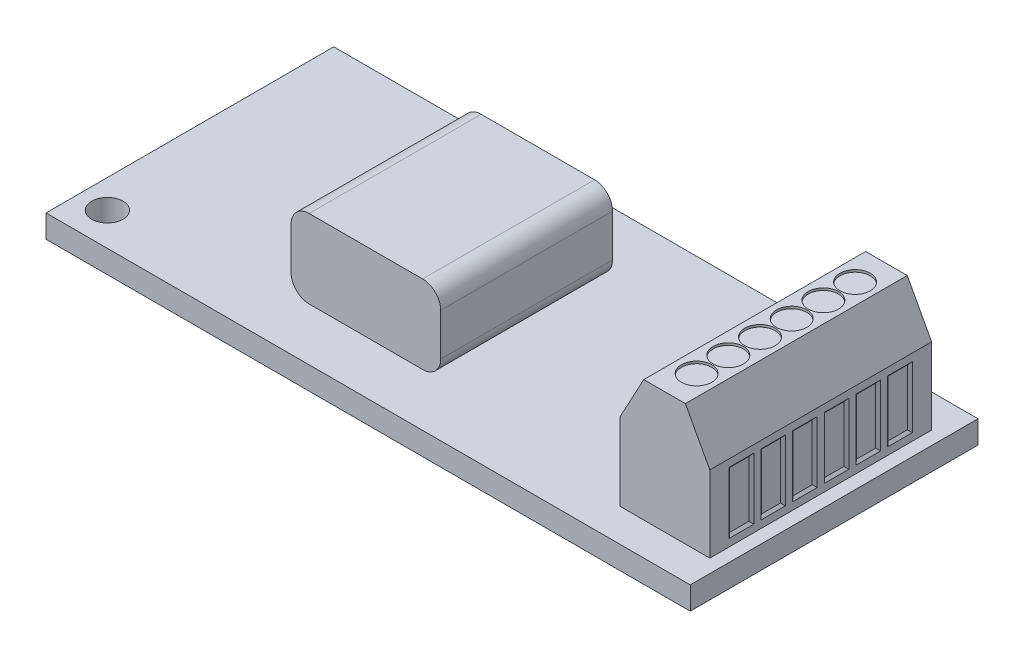
SolidWorks part; units mm, degrees
ref_plane "Front Plane" through (0, 0, 0) normal (0, 0, 1) x (1, 0, 0)
ref_plane "Top Plane" through (0, 0, 0) normal (0, 1, 0) x (1, 0, 0)
ref_plane "Right Plane" through (0, 0, 0) normal (1, 0, 0) x (0, 0, -1)
ref_axis "Axis1" through (-88.99, 0, 0) along (1, 0, 0)
ref_axis "Axis2" through (0, 55, 0) along (0, -1, 0)
ref_axis "Axis3" through (0, 0, 55) along (0, 0, -1)
ref_point "Point1"
sketch "Sketch1" plane through (0, 0, 0) normal (0, 1, 0) x (1, 0, 0)
  line L1 (-22.606, -10.0965) -> (22.606, -10.0965)
  line L2 (-22.606, -10.0965) -> (-22.606, 10.0965)
  line L3 (-22.606, 10.0965) -> (22.606, 10.0965)
  line L4 (22.606, -10.0965) -> (22.606, 10.0965)
  line L5 (-22.606, -10.0965) -> (22.606, 10.0965) construction
  line L6 (-22.606, 10.0965) -> (22.606, -10.0965) construction
  point P0 (0, 0)
  dimension "D1" = 20.193
  dimension "D2" = 45.212
extrude "Boss-Extrude1" add sketch "Sketch1" along normal mid plane 1.6002
sketch "Sketch2" plane through (0, 0.8001, 0) normal (0, 1, 0) x (1, 0, 0)
  line L0 (22.606, -10.0965) -> (22.606, 10.0965) construction
  line L1 (15.367, -7.7851) -> (21.6662, -7.7851)
  line L2 (15.367, -7.7851) -> (15.367, 7.7851)
  line L3 (15.367, 7.7851) -> (21.6662, 7.7851)
  line L4 (21.6662, -7.7851) -> (21.6662, 7.7851)
  line L5 (15.367, -7.7851) -> (21.6662, 7.7851) construction
  line L6 (15.367, 7.7851) -> (21.6662, -7.7851) construction
  line L7 (18.5166, 0) -> (0, 0) construction
  point P0 (18.5166, 0)
  dimension "D1" = 0.9398
  dimension "D2" = 6.2992
  dimension "D3" = 15.5702
extrude "Boss-Extrude2" add sketch "Sketch2" along normal blind 8.5344 separate body
sketch "Sketch3" plane through (0, 0, 7.7851) normal (0, 0, 1) x (1, 0, 0)
  line L0 (17.0319, 9.3345) -> (19.9529, 9.3345)
  line L1 (15.367, 9.3345) -> (21.6662, 9.3345) construction
  line L2 (19.9529, 9.3345) -> (21.6662, 6.1595)
  line L3 (21.6662, 9.3345) -> (21.6662, 0.8001) construction
  line L4 (21.6662, 6.1595) -> (21.6662, 9.3345) construction
  line L5 (18.4924, 9.3345) -> (18.4924, 6.9827) construction
  line L6 (17.0319, 9.3345) -> (15.3187, 6.1595)
  line L7 (15.3187, 6.1595) -> (15.3187, 11.2263)
  line L8 (15.3187, 11.2263) -> (21.6662, 11.2263)
  line L9 (21.6662, 11.2263) -> (21.6662, 6.1595)
  point P5 (18.4924, 9.3345)
  dimension "D1" = 2.921
  dimension "D2" = 3.175
sketch "Sketch4" plane through (0, 9.3345, 0) normal (0, 1, 0) x (1, 0, 0)
  line L0 (18.5166, 7.7851) -> (18.5166, 5.5608) construction
  line L2 (18.5166, 5.5608) -> (18.5166, 3.3365) construction
  line L3 (18.5166, 3.3365) -> (18.5166, 1.1122) construction
  line L4 (18.5166, 1.1122) -> (18.5166, -1.1122) construction
  line L5 (18.5166, -1.1122) -> (18.5166, -3.3365) construction
  line L6 (18.5166, -3.3365) -> (18.5166, -5.5608) construction
  line L7 (18.5166, -5.5608) -> (18.5166, -7.7851) construction
  circle A0 centre (18.5166, -5.5608) radius 1.0668
  circle A1 centre (18.5166, -3.3365) radius 1.0668
  circle A2 centre (18.5166, -1.1122) radius 1.0668
  circle A3 centre (18.5166, 1.1122) radius 1.0668
  circle A4 centre (18.5166, 3.3365) radius 1.0668
  circle A5 centre (18.5166, 5.5608) radius 1.0668
  dimension "D1" = 2.1336
sketch "Sketch6" plane through (0, 0.8001, 0) normal (0, 1, 0) x (1, 0, 0)
  line L0 (-21.717, -7.7773) -> (-22.606, -7.7773) construction
  line L1 (-22.606, 10.0965) -> (-22.606, -10.0965) construction
  line L2 (-20.617, -8.8773) -> (-20.617, -10.0965) construction
  line L3 (-22.606, -10.0965) -> (22.606, -10.0965) construction
  line L4 (12.906, 7.7465) -> (22.606, 7.7465) construction
  line L5 (22.606, -10.0965) -> (22.606, 10.0965) construction
  line L6 (11.806, 8.8465) -> (11.806, 10.0965) construction
  line L7 (22.606, 10.0965) -> (-22.606, 10.0965) construction
  circle A0 centre (-20.617, -7.7773) radius 1.1
  circle A1 centre (11.806, 7.7465) radius 1.1
  dimension "D1" = 0.889
  dimension "D3" = 2.2
  dimension "D4" = 9.7
  dimension "D6" = 2.2
  dimension "D2" = 1.2192
  dimension "D5" = 1.25
extrude "Cut-Extrude4" cut sketch "Sketch6" against normal through all
sketch "Sketch7" plane through (0, 0.8001, 0) normal (0, 1, 0) x (1, 0, 0)
  line L0 (-22.606, -10.0965) -> (22.606, -10.0965) construction
  line L1 (-9.106, -6.3965) -> (1.394, -6.3965)
  line L2 (-9.106, -6.3965) -> (-9.106, 5.6665)
  line L3 (-9.106, 5.6665) -> (1.394, 5.6665)
  line L4 (1.394, -6.3965) -> (1.394, 5.6665)
  line L5 (-9.106, -6.3965) -> (1.394, 5.6665) construction
  line L6 (-9.106, 5.6665) -> (1.394, -6.3965) construction
  line L7 (22.606, 10.0965) -> (-22.606, 10.0965) construction
  line L8 (-22.606, 10.0965) -> (-22.606, -10.0965) construction
  point P0 (-3.856, -0.365)
  dimension "D1" = 3.7
  dimension "D2" = 4.43
  dimension "D3" = 10.5
  dimension "D4" = 13.5
extrude "Boss-Extrude3" add sketch "Sketch7" along normal blind 5.5 separate body
extrude "Cut-Extrude5" cut sketch "Sketch3" against normal through all
extrude "Cut-Extrude6" cut sketch "Sketch4" against normal blind 0.1588
sketch "Sketch5" plane through (21.6662, 0, 0) normal (1, 0, 0) x (0, 0, -1)
  line L0 (-7.7851, 3.4798) -> (-5.5608, 3.4798) construction
  line L1 (-7.7851, 6.1595) -> (-7.7851, 0.8001) construction
  line L2 (-5.5608, 3.4798) -> (-3.3365, 3.4798) construction
  line L3 (-3.3365, 3.4798) -> (-1.1122, 3.4798) construction
  line L4 (-1.1122, 3.4798) -> (1.1122, 3.4798) construction
  line L5 (1.1122, 3.4798) -> (3.3365, 3.4798) construction
  line L6 (3.3365, 3.4798) -> (5.5608, 3.4798) construction
  line L7 (5.5608, 3.4798) -> (7.7851, 3.4798) construction
  line L8 (7.7851, 6.1595) -> (7.7851, 0.8001) construction
  line L10 (-6.4244, 1.3208) -> (-4.6972, 1.3208)
  line L11 (-6.4244, 1.3208) -> (-6.4244, 5.6388)
  line L12 (-6.4244, 5.6388) -> (-4.6972, 5.6388)
  line L13 (-4.6972, 1.3208) -> (-4.6972, 5.6388)
  line L14 (-6.4244, 1.3208) -> (-4.6972, 5.6388) construction
  line L15 (-6.4244, 5.6388) -> (-4.6972, 1.3208) construction
  line L16 (-4.2001, 1.3208) -> (-2.4729, 1.3208)
  line L17 (-4.2001, 1.3208) -> (-4.2001, 5.6388)
  line L18 (-4.2001, 5.6388) -> (-2.4729, 5.6388)
  line L19 (-2.4729, 1.3208) -> (-2.4729, 5.6388)
  line L20 (-4.2001, 1.3208) -> (-2.4729, 5.6388) construction
  line L21 (-4.2001, 5.6388) -> (-2.4729, 1.3208) construction
  line L22 (-1.9758, 1.3208) -> (-0.2486, 1.3208)
  line L23 (-1.9758, 1.3208) -> (-1.9758, 5.6388)
  line L24 (-1.9758, 5.6388) -> (-0.2486, 5.6388)
  line L25 (-0.2486, 1.3208) -> (-0.2486, 5.6388)
  line L26 (-1.9758, 1.3208) -> (-0.2486, 5.6388) construction
  line L27 (-1.9758, 5.6388) -> (-0.2486, 1.3208) construction
  line L28 (0.2486, 1.3208) -> (1.9758, 1.3208)
  line L29 (0.2486, 1.3208) -> (0.2486, 5.6388)
  line L30 (0.2486, 5.6388) -> (1.9758, 5.6388)
  line L31 (1.9758, 1.3208) -> (1.9758, 5.6388)
  line L32 (0.2486, 1.3208) -> (1.9758, 5.6388) construction
  line L33 (0.2486, 5.6388) -> (1.9758, 1.3208) construction
  line L34 (4.6972, 1.3208) -> (6.4244, 1.3208)
  line L35 (4.6972, 1.3208) -> (4.6972, 5.6388)
  line L36 (4.6972, 5.6388) -> (6.4244, 5.6388)
  line L37 (6.4244, 1.3208) -> (6.4244, 5.6388)
  line L38 (4.6972, 1.3208) -> (6.4244, 5.6388) construction
  line L39 (4.6972, 5.6388) -> (6.4244, 1.3208) construction
  line L40 (2.4729, 1.3208) -> (4.2001, 1.3208)
  line L41 (2.4729, 1.3208) -> (2.4729, 5.6388)
  line L42 (2.4729, 5.6388) -> (4.2001, 5.6388)
  line L43 (4.2001, 1.3208) -> (4.2001, 5.6388)
  line L44 (2.4729, 1.3208) -> (4.2001, 5.6388) construction
  line L45 (2.4729, 5.6388) -> (4.2001, 1.3208) construction
  dimension "D1" = 1.7272
  dimension "D2" = 4.318
extrude "Cut-Extrude7" cut sketch "Sketch5" against normal blind 0.1588 draft 50
fillet "Fillet1" radius 1.27 4 edges at (-9.106, 0.8001, 0.365) (-9.106, 6.3001, 0.365) (1.394, 6.3001, 0.365) (1.394, 0.8001, 0.365)
sketch "Sketch8" plane through (0, -0.8001, 0) normal (0, -1, 0) x (1, 0, 0)
  line L1 (4.106, -4.4212) -> (9.106, -4.4212)
  line L2 (4.106, -4.4212) -> (4.106, -9.4212)
  line L3 (4.106, -9.4212) -> (9.106, -9.4212)
  line L4 (9.106, -4.4212) -> (9.106, -9.4212)
  line L5 (4.106, -4.4212) -> (9.106, -9.4212) construction
  line L6 (4.106, -9.4212) -> (9.106, -4.4212) construction
  line L7 (22.606, 10.0965) -> (22.606, -10.0965) construction
  point P0 (6.606, -6.9212)
  dimension "D1" = 5
  dimension "D2" = 5
  dimension "D3" = 18.5
extrude "Boss-Extrude4" add sketch "Sketch8" along normal blind 2.17 separate body
